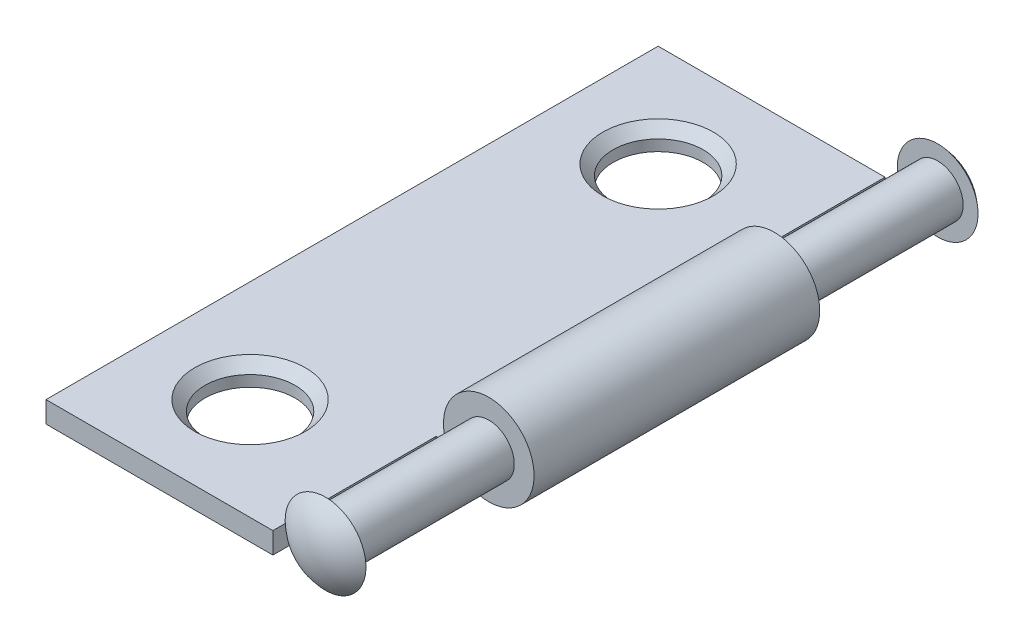
SolidWorks part; units mm, degrees
material "Chrome Stainless Steel"
ref_plane "Front Plane" through (0, 0, 0) normal (0, 0, 1) x (1, 0, 0)
ref_plane "Top Plane" through (0, 0, 0) normal (0, 1, 0) x (1, 0, 0)
ref_plane "Right Plane" through (0, 0, 0) normal (1, 0, 0) x (0, 0, -1)
sketch "Sketch2" plane through (0, 0, 0) normal (0, 0, 1) x (1, 0, 0)
  circle A0 centre (0, 0) radius 1.5875
  circle A1 centre (0, 0) radius 2.8194
  dimension "D1" = 5.6388
  dimension "D2" = 3.175
extrude "Boss-Extrude1" add sketch "Sketch2" along normal mid plane 38.1
sketch "Sketch3" plane through (0, 0, 0) normal (0, 0, 1) x (1, 0, 0)
  line L1 (-1.7018, -2.2479) -> (-17.399, -2.2479)
  line L3 (-2.6626, -0.9271) -> (-17.399, -0.9271)
  line L4 (-17.399, -2.2479) -> (-17.399, -0.9271)
  circle A1 centre (0, 0) radius 2.8194 construction
  arc A2 (-2.6626, -0.9271) -> (-1.7018, -2.2479) centre (0, 0) ccw
  circle A3 centre (0, 0) radius 1.5875 construction
  point P0 (-17.399, -1.5875)
  point P2 (0, -1.5875)
  point P7 (-2.8194, 0)
  point P8 (17.2876, -1.8526)
  point P14 (0, 0)
  point P15 (0, 0)
  point P16 (0, 0)
  point P17 (-2.8122, 0.2013)
  dimension "D2" = 14.5796
  dimension "D1" = 1.3208
extrude "Boss-Extrude2" add sketch "Sketch3" along normal up to surface and the other way up to surface up to face at (2.8194, 0, 19.05) other way up to face at (2.8194, 0, -19.05)
fillet "Fillet1" radius 2.54 1 edges at (-1.7018, -2.2479, 0)
sketch "Sketch4" plane through (0, 0, 0) normal (0, 0, 1) x (1, 0, 0)
  line L0 (-17.399, -0.9271) -> (-17.399, -2.2479) construction
  line L1 (3.2766, 3.2766) -> (-3.2766, 3.2766)
  line L2 (3.2766, 3.2766) -> (3.2766, -3.2766)
  line L3 (3.2766, -3.2766) -> (-3.2766, -3.2766)
  line L4 (-3.2766, 3.2766) -> (-3.2766, -3.2766)
  line L5 (3.2766, 3.2766) -> (-3.2766, -3.2766) construction
  line L6 (3.2766, -3.2766) -> (-3.2766, 3.2766) construction
  point P0 (0, 0)
  dimension "D1" = 14.1224
extrude "Cut-Extrude1" cut sketch "Sketch4" along normal through all from offset 8.89
extrude "Cut-Extrude2" cut sketch "Sketch4<2>" against normal through all from offset 8.89 offset against normal yes
sketch "Sketch4<2>" plane through (0, 0, 0) normal (0, 0, 1) x (1, 0, 0) same geometry as "Sketch4"
hole_wizard "#10 Clearance Hole1" positions "Sketch5" profile "Sketch6" hole size "#10" standard "ANSI Inch" end condition through all
sketch "Sketch5" plane through (0, -0.9271, 0) normal (0, -1, 0) x (-1, 0, 0)
  line L0 (11.049, 12.7) -> (11.049, -12.7) construction
  line L2 (3.2766, 19.05) -> (17.399, 19.05) construction
  line L3 (17.399, -19.05) -> (17.399, 19.05) construction
  point P0 (11.049, 12.7)
  point P2 (11.049, -12.7)
  point P9 (11.049, 0)
  dimension "D1" = 6.35
  dimension "D2" = 6.35
sketch "Sketch6" plane through (-11.049, -0.9271, -12.7) normal (1, 0, 0) x (0, 0, 1)
  line L0 (0, 0) -> (0, 1.8923)
  line L1 (0, 1.8923) -> (2.8067, 1.8923)
  line L2 (2.8067, 1.8923) -> (2.8067, 0.635)
  line L3 (2.8067, 0.635) -> (3.4417, 0)
  line L5 (3.4417, 0) -> (0, 0)
  line L6 (-2.8067, 0.635) -> (-3.4417, 0) construction
  line L11 (0, -6.35) -> (0, 107.95) construction
  dimension "Thru Hole Dia." = 5.6134
  dimension "Thru Hole Depth" = 1.8923
  dimension "Near C'Sink Dia." = 6.8834
  dimension "Near C'Sink Angle" = 90
sketch "Sketch8" plane through (0, 0, 0) normal (0, 1, 0) x (1, 0, 0)
  line L0 (0, 20.066) -> (0, -20.066)
  line L1 (-2.5146, -19.05) -> (-1.5875, -19.05)
  line L2 (-1.5875, -19.05) -> (-1.5875, 19.05)
  line L3 (-1.5875, 19.05) -> (-2.5146, 19.05)
  line L5 (-3.2766, -19.05) -> (-17.399, -19.05) construction
  line L6 (-17.399, 19.05) -> (-3.2766, 19.05) construction
  arc A0 (0, -20.066) -> (-2.5146, -19.05) centre (0, -16.4462) cw
  arc A1 (0, 20.066) -> (-2.5146, 19.05) centre (0, 16.4462) ccw
  point P15 (0, 0)
  point P16 (-2.3541, -19.05)
  dimension "D1" = 1.016
  dimension "D2" = 2.5146
revolve "Revolve1" add sketch "Sketch8" angle 360 about L0
